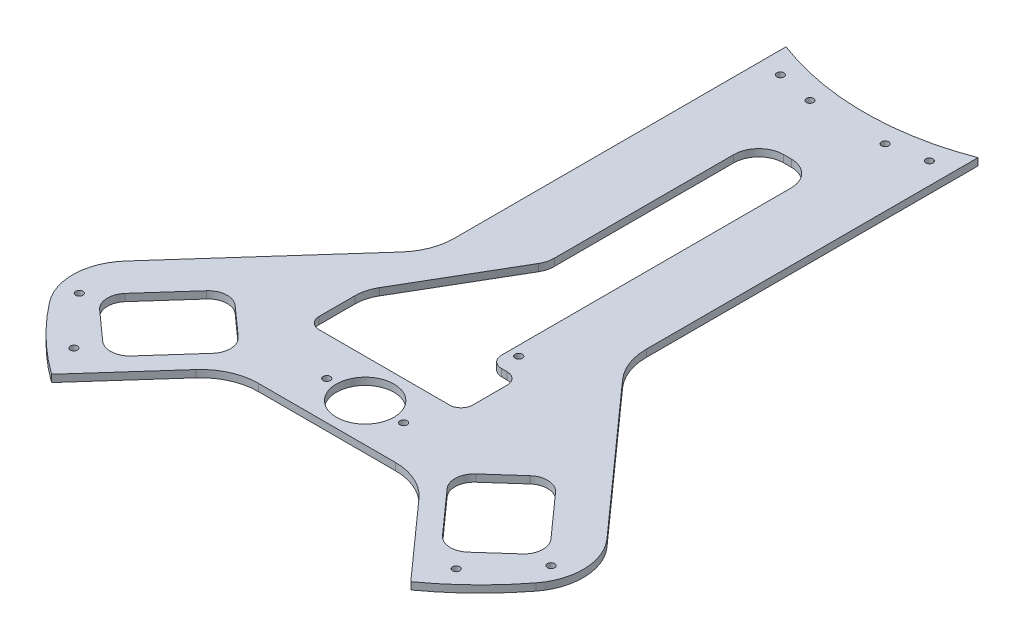
SolidWorks part; units mm, degrees
ref_plane "Front Plane" through (0, 0, 0) normal (0, 0, 1) x (1, 0, 0)
ref_plane "Top Plane" through (0, 0, 0) normal (0, 1, 0) x (1, 0, 0)
ref_plane "Right Plane" through (0, 0, 0) normal (1, 0, 0) x (0, 0, -1)
sketch "Sketch1" plane through (0, 0, 0) normal (0, 1, 0) x (1, 0, 0)
  line L0 (-63.5, 31.75) -> (-178.5164, -97.0677)
  line L1 (-215.9, 31.75) -> (215.9, 31.75)
  line L2 (-215.9, 31.75) -> (-215.9, -31.75)
  line L3 (-215.9, -31.75) -> (215.9, -31.75)
  line L4 (215.9, 31.75) -> (215.9, -31.75)
  line L5 (-215.9, 31.75) -> (215.9, -31.75) construction
  line L6 (-215.9, -31.75) -> (215.9, 31.75) construction
  line L7 (63.5, 31.75) -> (-63.5, 31.75)
  line L8 (63.5, 31.75) -> (63.5, 292.608)
  line L9 (63.5, 292.608) -> (-63.5, 292.608)
  line L10 (-63.5, 31.75) -> (-63.5, 292.608)
  line L11 (0, -31.75) -> (-118.8264, -164.8348)
  line L12 (0, -31.75) -> (118.8264, -164.8348)
  line L13 (63.5, 31.75) -> (178.5164, -97.0677)
  line L14 (-62.3664, -101.6) -> (62.3664, -101.6)
  circle A1 centre (0, 0) radius 25.4 construction
  circle A2 centre (-25.4, 0) radius 2.3813
  circle A3 centre (25.4, 0) radius 2.3812
  circle A4 centre (0, 0) radius 203.2
  circle A5 centre (0, -76.2) radius 25.4 construction
  circle A6 centre (-25.4, -76.2) radius 2.3813
  circle A7 centre (25.4, -76.2) radius 2.3813
  point P0 (0, 0)
  dimension "D5" = 4.7625
  dimension "D6" = 4.7625
  dimension "D7" = 101.6
  dimension "D8" = 50.8
  dimension "D10" = 406.4
  dimension "D14" = 4.7625
  dimension "D15" = 4.7625
  dimension "D16" = 50.8
  dimension "D1" = 431.8
  dimension "D2" = 63.5
  dimension "D3" = 127
  dimension "D4" = 63.5
  dimension "D9" = 260.858
  dimension "D11" = 59.69
  dimension "D12" = 59.69
  dimension "D13" = 76.2
extrude "Boss-Extrude1" add sketch "Sketch1" along normal blind 4.7625 contours L10 L1 L8 L9 | L4 L1 L2 L3 A3 A2 | L0 A4 L11 L3 | L12 A4 L13 L3 | A4 L8 L9 L10 | L11 L14 L12 region at (0, 0, 3.2765) region at (0, 0, -115.8234) region at (-100.5416, 0, 84.5084) region at (0, 0, -246.176) region at (0, 0, 78.3341) region at (100.5416, 0, 84.5084)
sketch "Sketch2" plane through (0, 4.7625, 0) normal (0, 1, 0) x (1, 0, 0)
  line L0 (0, 292.608) -> (0, -101.6) construction
  line L1 (63.5, 292.608) -> (-63.5, 292.608) construction
  line L2 (-62.3664, -101.6) -> (62.3664, -101.6) construction
  circle A0 centre (25.4, 279.908) radius 2.3813
  circle A1 centre (50.8, 279.908) radius 2.3813
  circle A2 centre (-50.8, 279.908) radius 2.3813
  circle A3 centre (-25.4, 279.908) radius 2.3813
  dimension "D3" = 4.7625
  dimension "D4" = 4.7625
  dimension "D1" = 25.4
  dimension "D2" = 50.8
  dimension "D5" = 12.7
  dimension "D6" = 12.7
extrude "Cut-Extrude1" cut sketch "Sketch2" against normal through all
fillet "Fillet1" radius 38.1 4 edges at (63.5, 2.3813, -31.75) (-63.5, 2.3813, -31.75) (62.3664, 2.3813, 101.6) (-62.3664, 2.3813, 101.6)
sketch "Sketch4" plane through (0, 4.7625, 0) normal (0, 1, 0) x (1, 0, 0)
  line L0 (0, 292.608) -> (0, 0) construction
  line L1 (63.5, 292.608) -> (-63.5, 292.608) construction
  line L2 (0, 0) -> (0, -190.5) construction
  line L3 (0, 0) -> (-156.0485, -109.2663) construction
  circle A0 centre (0, 0) radius 190.5 construction
  circle A1 centre (-156.0485, -109.2663) radius 2.3813
  circle A2 centre (-126.4791, -142.4545) radius 2.3813
  circle A3 centre (126.4791, -142.4545) radius 2.3813
  circle A4 centre (156.0485, -109.2663) radius 2.3813
  dimension "D1" = 381
  dimension "D4" = 4.7625
  dimension "D5" = 4.7625
  dimension "D2" = 44.45
  dimension "D3" = 55
extrude "Cut-Extrude3" cut sketch "Sketch4" against normal through all
fillet "Fillet2" radius 38.1 2 edges at (178.5164, 2.3813, 97.0677) (-178.5164, 2.3813, 97.0677)
sketch "Sketch5" plane through (0, 4.7625, 0) normal (0, 1, 0) x (1, 0, 0)
  line L0 (-149.2765, -103.5959) -> (-111.3829, -137.4296)
  line L1 (-149.2765, -103.5959) -> (-106.9843, -56.229)
  line L2 (-111.3829, -137.4296) -> (-69.0908, -90.0627)
  line L3 (-106.9843, -56.229) -> (-69.0908, -90.0627)
  line L8 (-73.7278, -114.3247) -> (-118.8264, -164.8348) construction
  line L9 (0, 292.608) -> (0, -101.6) construction
  line L10 (63.5, 292.608) -> (-63.5, 292.608) construction
  line L11 (106.9843, -56.229) -> (69.0908, -90.0627)
  line L12 (111.3829, -137.4296) -> (69.0908, -90.0627)
  line L13 (149.2765, -103.5959) -> (106.9843, -56.229)
  line L14 (149.2765, -103.5959) -> (111.3829, -137.4296)
  line L15 (-45.3077, -101.6) -> (45.3077, -101.6) construction
  dimension "D1" = 50.8
  dimension "D2" = 12.7
  dimension "D3" = 63.5
  dimension "D4" = 25.4
extrude "Cut-Extrude4" cut sketch "Sketch5" against normal through all
fillet "Fillet3" radius 12.7 8 edges at (111.3829, 2.3813, 137.4296) (69.0908, 2.3813, 90.0627) (106.9843, 2.3813, 56.229) (149.2765, 2.3813, 103.5959) (-69.0908, 2.3813, 90.0627) (-106.9843, 2.3813, 56.229) (-149.2765, 2.3813, 103.5959) (-111.3829, 2.3813, 137.4296)
sketch "Sketch6" plane through (0, 4.7625, 0) normal (0, 1, 0) x (1, 0, 0)
  circle A0 centre (0, -76.2) radius 19.05
  dimension "D1" = 38.1
  dimension "D2" = 76.2
extrude "Cut-Extrude5" cut sketch "Sketch6" against normal through all
sketch "Sketch7" plane through (0, 4.7625, 0) normal (0, 1, 0) x (1, 0, 0)
  line L0 (-45.3077, -101.6) -> (45.3077, -101.6) construction
  line L1 (-19.05, 203.2) -> (19.05, 203.2)
  line L2 (-19.05, 203.2) -> (-19.05, -50.8)
  line L3 (-19.05, -50.8) -> (19.05, -50.8)
  line L4 (19.05, 203.2) -> (19.05, -50.8)
  line L5 (-19.05, 203.2) -> (19.05, -50.8) construction
  line L6 (-19.05, -50.8) -> (19.05, 203.2) construction
  point P0 (0, 76.2)
  dimension "D1" = 38.1
  dimension "D2" = 50.8
  dimension "D3" = 254
extrude "Cut-Extrude6" cut sketch "Sketch7" against normal through all
sketch "Sketch8" plane through (0, 4.7625, 0) normal (0, 1, 0) x (1, 0, 0)
  line L0 (-19.05, -50.8) -> (19.05, -50.8) construction
  line L1 (-63.5, -50.8) -> (38.1, -50.8)
  line L2 (-63.5, -50.8) -> (-63.5, -12.7)
  line L3 (-63.5, -12.7) -> (38.1, -12.7)
  line L4 (38.1, -50.8) -> (38.1, -12.7)
  dimension "D1" = 101.6
  dimension "D2" = 38.1
  dimension "D3" = 38.1
extrude "Cut-Extrude7" cut sketch "Sketch8" against normal through all
sketch "Sketch9" plane through (0, 4.7625, 0) normal (0, 1, 0) x (1, 0, 0)
  line L0 (-63.5, -12.7) -> (-19.05, 63.5)
  line L1 (-19.05, 203.2) -> (-19.05, -12.7) construction
  line L2 (-19.05, 63.5) -> (-19.05, -12.7)
  line L3 (-19.05, -12.7) -> (-63.5, -12.7)
  dimension "D1" = 76.2
extrude "Cut-Extrude8" cut sketch "Sketch9" against normal through all
fillet "Fillet4" radius 25.4 1 edges at (-63.5, 2.3813, 12.7)
fillet "Fillet5" radius 7.62 4 edges at (-63.5, 2.3813, 50.8) (38.1, 2.3813, 50.8) (38.1, 2.3813, 12.7) (19.05, 2.3813, 12.7)
fillet "Fillet8" radius 16.51 3 edges at (-19.05, 2.3813, -203.2) (19.05, 2.3813, -203.2) (-19.05, 2.3813, -63.5)
sketch "Sketch10" plane through (0, 4.7625, 0) normal (0, 1, 0) x (1, 0, 0)
  line L0 (0, 431.8) -> (0, 0) construction
  line L1 (0, 431.8) -> (-24.8652, 242.9298) construction
  line L2 (0, 431.8) -> (-49.305, 247.7911) construction
  circle A0 centre (0, 431.8) radius 177.8
  circle A1 centre (0, 431.8) radius 190.5 construction
  circle A2 centre (-49.305, 247.7911) radius 2.3812
  circle A3 centre (-24.8652, 242.9298) radius 2.3813
  circle A6 centre (24.8652, 242.9298) radius 2.3813
  circle A7 centre (49.305, 247.7911) radius 2.3812
  dimension "D1" = 355.6
  dimension "D3" = 381
  dimension "D4" = 4.7625
  dimension "D5" = 4.7625
  dimension "D6" = 7.5
  dimension "D7" = 15
  dimension "D2" = 431.8
extrude "Cut-Extrude9" cut sketch "Sketch10" against normal through all
